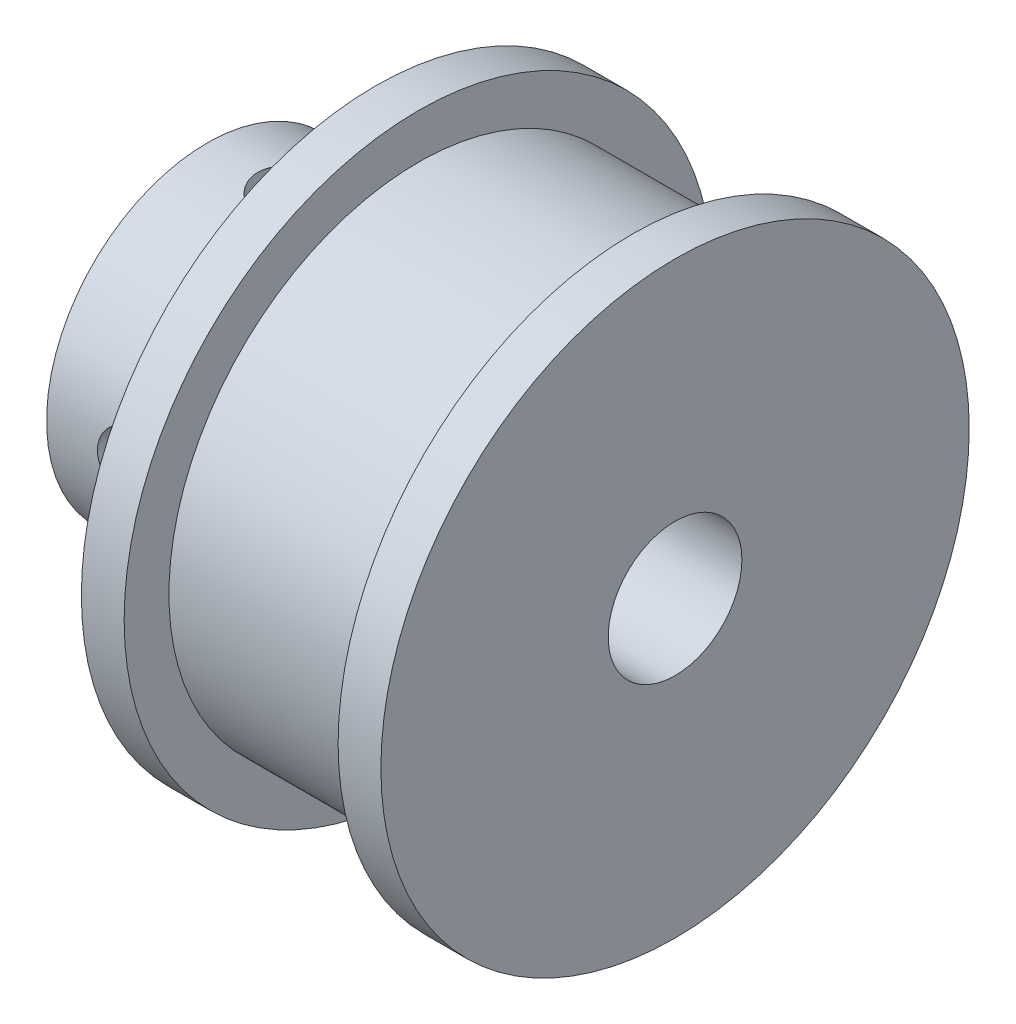
SolidWorks part; units mm, degrees
material "6061-T6 (SS)"
ref_plane "Front Plane" through (0, 0, 0) normal (0, 0, 1) x (1, 0, 0)
ref_plane "Top Plane" through (0, 0, 0) normal (0, 1, 0) x (1, 0, 0)
ref_plane "Right Plane" through (0, 0, 0) normal (1, 0, 0) x (0, 0, -1)
sketch "Sketch1" plane through (0, 0, 0) normal (0, 0, 1) x (1, 0, 0)
  line L0 (0, 2.5) -> (0, 6)
  line L1 (6.3, 11) -> (7.9, 11)
  line L2 (7.9, 11) -> (7.9, 9.325)
  line L3 (7.9, 9.325) -> (15.9, 9.325)
  line L4 (15.9, 9.325) -> (15.9, 11)
  line L5 (15.9, 11) -> (17.5, 11)
  line L6 (17.5, 11) -> (17.5, 2.5)
  line L7 (17.5, 2.5) -> (0, 2.5)
  line L8 (0, 0) -> (-7.6744, 0) construction
  line L9 (6.3, 11) -> (6.3, 6)
  line L10 (6.3, 6) -> (0, 6)
  dimension "D1" = 5
  dimension "D2" = 22
  dimension "D3" = 18.65
  dimension "D4" = 11.2
  dimension "D5" = 17.5
  dimension "D6" = 1.6
  dimension "D7" = 12
revolve "Revolve1" add sketch "Sketch1" angle 360 about L8
hole_wizard "M3x0.5 Tapped Hole1" positions "Sketch3" profile "Sketch2" tap size "M3x0.5" standard "ANSI Metric" end condition through all
sketch "Sketch3" plane through (0, 0, 0) normal (0, 1, 0) x (1, 0, 0)
  line L0 (0, 0) -> (6.3, 0) construction
  line L2 (6.3, 6) -> (6.3, -6) construction
  point P8 (3.15, 0)
sketch "Sketch2" plane through (3.15, 0, 0) normal (1, 0, 0) x (0, 0, -1)
  line L0 (0, 0) -> (0, 11)
  line L1 (0, 11) -> (1.25, 11)
  line L2 (1.25, 11) -> (1.25, 0)
  line L5 (1.25, 0) -> (0, 0)
  line L11 (0, -6.35) -> (0, 107.95) construction
  dimension "Thread Major Dia." = 2.5
  dimension "Thru Tap Drill Depth" = 11
hole_wizard "M3x0.5 Tapped Hole2" positions "Sketch5" profile "Sketch4" tap size "M3x0.5" standard "ANSI Metric" end condition through all
sketch "Sketch5" plane through (0, 0, 0) normal (0, 0, 1) x (1, 0, 0)
  line L0 (0, 0) -> (6.3, 0) construction
  line L2 (6.3, 11) -> (6.3, -11) construction
  point P7 (3.15, 0)
sketch "Sketch4" plane through (3.15, 0, 0) normal (1, 0, 0) x (0, 1, 0)
  line L0 (0, 0) -> (0, 11)
  line L1 (0, 11) -> (1.25, 11)
  line L2 (1.25, 11) -> (1.25, 0)
  line L5 (1.25, 0) -> (0, 0)
  line L11 (0, -6.35) -> (0, 107.95) construction
  dimension "Thread Major Dia." = 2.5
  dimension "Thru Tap Drill Depth" = 11
